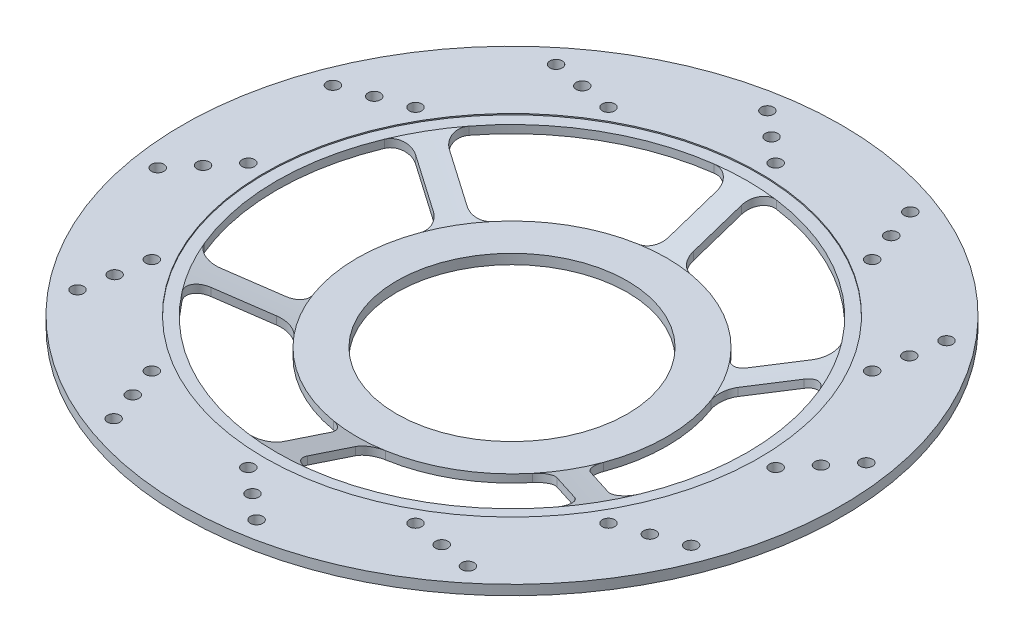
SolidWorks part; units mm, degrees
material "A286 Iron Base Superalloy"
ref_plane "Front" through (0, 0, 0) normal (0, 0, 1) x (1, 0, 0)
ref_plane "Top" through (0, 0, 0) normal (0, 1, 0) x (1, 0, 0)
ref_plane "Right" through (0, 0, 0) normal (1, 0, 0) x (0, 0, -1)
sketch "Sketch1" plane through (0, 0, 0) normal (0, 0, 1) x (1, 0, 0)
  line L0 (0, 0) -> (0, 36.9309) construction
  line L1 (0, 0) -> (70, 0) construction
  line L2 (70, 0) -> (90.5263, 0)
  line L3 (90.5263, 0) -> (143.5436, 17.6)
  line L4 (143.5436, 17.6) -> (200, 17.6)
  line L5 (70, 6) -> (94, 6)
  line L6 (94, 6) -> (142.8, 22.2)
  line L7 (142.8, 22.2) -> (200, 22.2)
  line L8 (200, 17.6) -> (200, 22.2)
  line L9 (70, 0) -> (70, 6)
  dimension "D2" = 22.2
  dimension "D3" = 57.2
  dimension "D4" = 24
  dimension "D5" = 140
  dimension "D6" = 400
  dimension "D7" = 6
  dimension "D1" = 4.6
  dimension "D8" = 4.6
revolve "Revolve2" add sketch "Sketch1" angle 360 about L0
sketch "Sketch3" plane through (0, 22.2, 0) normal (0, 1, 0) x (1, 0, 0)
  line L0 (0, 0) -> (0, 200) construction
  line L1 (0, 0) -> (173.2051, 100) construction
  line L2 (7.5, 102.5171) -> (7.5, 131.6419)
  line L3 (85.0324, 57.7537) -> (110.2552, 72.3161)
  line L4 (7.5, 0) -> (7.5, 200) construction
  line L5 (-3.75, 6.4952) -> (169.4551, 106.4952) construction
  line L6 (92.5324, 44.7633) -> (117.7552, 59.3258)
  line L7 (92.5324, -44.7633) -> (117.7552, -59.3258)
  line L8 (85.0324, -57.7537) -> (110.2552, -72.3161)
  line L9 (7.5, -102.5171) -> (7.5, -131.6419)
  line L10 (-7.5, -102.5171) -> (-7.5, -131.6419)
  line L11 (-85.0324, -57.7537) -> (-110.2552, -72.3161)
  line L12 (-92.5324, -44.7633) -> (-117.7552, -59.3258)
  line L13 (-92.5324, 44.7633) -> (-117.7552, 59.3258)
  line L14 (-85.0324, 57.7537) -> (-110.2552, 72.3161)
  line L15 (-7.5, 102.5171) -> (-7.5, 131.6419)
  circle A0 centre (0, 0) radius 200 construction
  circle A1 centre (0, 39) radius 4
  arc A3 (113.1811, 87.074) -> (18.8178, 141.5547) centre (0, 0) ccw
  arc A4 (7.5, 102.5171) -> (15.8173, 92.6597) centre (17.5, 102.5171) ccw
  arc A5 (72.337, 60.028) -> (15.8173, 92.6597) centre (0, 0) ccw
  arc A6 (72.337, 60.028) -> (85.0324, 57.7537) centre (80.0324, 66.414) ccw
  arc A7 (110.2552, 72.3161) -> (113.1811, 87.074) centre (105.2552, 80.9764) ccw
  arc A8 (18.8178, 141.5547) -> (7.5, 131.6419) centre (17.5, 131.6419) ccw
  circle A9 centre (0, 0) radius 142.8 construction
  circle A10 centre (0, 0) radius 94 construction
  arc A11 (88.1543, -32.6316) -> (88.1543, 32.6316) centre (0, 0) ccw
  arc A12 (92.5324, 44.7633) -> (88.1543, 32.6316) centre (97.5324, 36.1031) ccw
  arc A13 (131.9988, 54.4807) -> (117.7552, 59.3258) centre (122.7552, 50.6655) ccw
  arc A14 (131.9988, -54.4807) -> (131.9988, 54.4807) centre (0, 0) ccw
  arc A15 (117.7552, -59.3258) -> (131.9988, -54.4807) centre (122.7552, -50.6655) ccw
  arc A16 (88.1543, -32.6316) -> (92.5324, -44.7633) centre (97.5324, -36.1031) ccw
  arc A17 (15.8173, -92.6597) -> (72.337, -60.028) centre (0, 0) ccw
  arc A18 (85.0324, -57.7537) -> (72.337, -60.028) centre (80.0324, -66.414) ccw
  arc A19 (113.1811, -87.074) -> (110.2552, -72.3161) centre (105.2552, -80.9764) ccw
  arc A20 (18.8178, -141.5547) -> (113.1811, -87.074) centre (0, 0) ccw
  arc A21 (7.5, -131.6419) -> (18.8178, -141.5547) centre (17.5, -131.6419) ccw
  arc A22 (15.8173, -92.6597) -> (7.5, -102.5171) centre (17.5, -102.5171) ccw
  arc A23 (-72.337, -60.028) -> (-15.8173, -92.6597) centre (0, 0) ccw
  arc A24 (-7.5, -102.5171) -> (-15.8173, -92.6597) centre (-17.5, -102.5171) ccw
  arc A25 (-18.8178, -141.5547) -> (-7.5, -131.6419) centre (-17.5, -131.6419) ccw
  arc A26 (-113.1811, -87.074) -> (-18.8178, -141.5547) centre (0, 0) ccw
  arc A27 (-110.2552, -72.3161) -> (-113.1811, -87.074) centre (-105.2552, -80.9764) ccw
  arc A28 (-72.337, -60.028) -> (-85.0324, -57.7537) centre (-80.0324, -66.414) ccw
  arc A29 (-88.1543, 32.6316) -> (-88.1543, -32.6316) centre (0, 0) ccw
  arc A30 (-92.5324, -44.7633) -> (-88.1543, -32.6316) centre (-97.5324, -36.1031) ccw
  arc A31 (-131.9988, -54.4807) -> (-117.7552, -59.3258) centre (-122.7552, -50.6655) ccw
  arc A32 (-131.9988, 54.4807) -> (-131.9988, -54.4807) centre (0, 0) ccw
  arc A33 (-117.7552, 59.3258) -> (-131.9988, 54.4807) centre (-122.7552, 50.6655) ccw
  arc A34 (-88.1543, 32.6316) -> (-92.5324, 44.7633) centre (-97.5324, 36.1031) ccw
  arc A35 (-15.8173, 92.6597) -> (-72.337, 60.028) centre (0, 0) ccw
  arc A36 (-85.0324, 57.7537) -> (-72.337, 60.028) centre (-80.0324, 66.414) ccw
  arc A37 (-113.1811, 87.074) -> (-110.2552, 72.3161) centre (-105.2552, 80.9764) ccw
  arc A38 (-18.8178, 141.5547) -> (-113.1811, 87.074) centre (0, 0) ccw
  arc A39 (-7.5, 131.6419) -> (-18.8178, 141.5547) centre (-17.5, 131.6419) ccw
  arc A40 (-15.8173, 92.6597) -> (-7.5, 102.5171) centre (-17.5, 102.5171) ccw
  circle A41 centre (33.775, 19.5) radius 4
  circle A42 centre (33.775, -19.5) radius 4
  circle A43 centre (0, -39) radius 4
  circle A44 centre (-33.775, -19.5) radius 4
  circle A45 centre (-33.775, 19.5) radius 4
  point P91 (0, 0)
  point P102 (0, 0)
  dimension "D3" = 8
  dimension "D6" = 10
  dimension "D2" = 39
  dimension "D1" = 60
  dimension "D4" = 7.5
  dimension "D5" = 7.5
  dimension "D7" = 6
  dimension "D8" = 6
extrude "Cut-Extrude1" cut sketch "Sketch3" against normal through all
sketch "Sketch4" plane through (0, 22.2, 0) normal (0, 1, 0) x (1, 0, 0)
  circle A0 centre (0, 0) radius 200
  circle A1 centre (0, 0) radius 150
  circle A2 centre (0, 0) radius 200 construction
  dimension "D1" = 50
extrude "Boss-Extrude1" add sketch "Sketch4" along normal blind 0.7
extrude "Boss-Extrude2" add sketch "Sketch4<2>" against normal blind 0.7 from surface starting at face at (0, 17.6, -200)
sketch "Sketch4<2>" plane through (0, 22.2, 0) normal (0, 1, 0) x (1, 0, 0) same geometry as "Sketch4"
sketch "Sketch5" plane through (0, 22.9, 0) normal (0, 1, 0) x (1, 0, 0)
  circle A0 centre (-30, 185) radius 3.75
  circle A1 centre (-15, 172.5) radius 3.75
  circle A2 centre (0, 160) radius 3.75
  circle A3 centre (0, 0) radius 150 construction
  circle A4 centre (0, 0) radius 200 construction
  circle A5 centre (80, 138.5641) radius 3.75
  circle A6 centre (73.2596, 156.8894) radius 3.75
  circle A7 centre (66.5192, 175.2147) radius 3.75
  circle A8 centre (138.5641, 80) radius 3.75
  circle A9 centre (141.8894, 99.2404) radius 3.75
  circle A10 centre (145.2147, 118.4808) radius 3.75
  circle A11 centre (160, 0) radius 3.75
  circle A12 centre (172.5, 15) radius 3.75
  circle A13 centre (185, 30) radius 3.75
  circle A14 centre (138.5641, -80) radius 3.75
  circle A15 centre (156.8894, -73.2596) radius 3.75
  circle A16 centre (175.2147, -66.5192) radius 3.75
  circle A17 centre (80, -138.5641) radius 3.75
  circle A18 centre (99.2404, -141.8894) radius 3.75
  circle A19 centre (118.4808, -145.2147) radius 3.75
  circle A20 centre (0, -160) radius 3.75
  circle A21 centre (15, -172.5) radius 3.75
  circle A22 centre (30, -185) radius 3.75
  circle A23 centre (-80, -138.5641) radius 3.75
  circle A24 centre (-73.2596, -156.8894) radius 3.75
  circle A25 centre (-66.5192, -175.2147) radius 3.75
  circle A26 centre (-138.5641, -80) radius 3.75
  circle A27 centre (-141.8894, -99.2404) radius 3.75
  circle A28 centre (-145.2147, -118.4808) radius 3.75
  circle A29 centre (-160, 0) radius 3.75
  circle A30 centre (-172.5, -15) radius 3.75
  circle A31 centre (-185, -30) radius 3.75
  circle A32 centre (-138.5641, 80) radius 3.75
  circle A33 centre (-156.8894, 73.2596) radius 3.75
  circle A34 centre (-175.2147, 66.5192) radius 3.75
  circle A35 centre (-80, 138.5641) radius 3.75
  circle A36 centre (-99.2404, 141.8894) radius 3.75
  circle A37 centre (-118.4808, 145.2147) radius 3.75
  point P79 (0, 0)
  dimension "D1" = 7.5
  dimension "D4" = 15
  dimension "D5" = 12.5
  dimension "D6" = 12.5
  dimension "D7" = 400
  dimension "D9" = 88.4808
  dimension "D10" = 97.014
  dimension "D2" = 160
  dimension "D3" = 15
  dimension "D8" = 12
extrude "Cut-Extrude3" cut sketch "Sketch5" against normal up to next (6 mm away)
